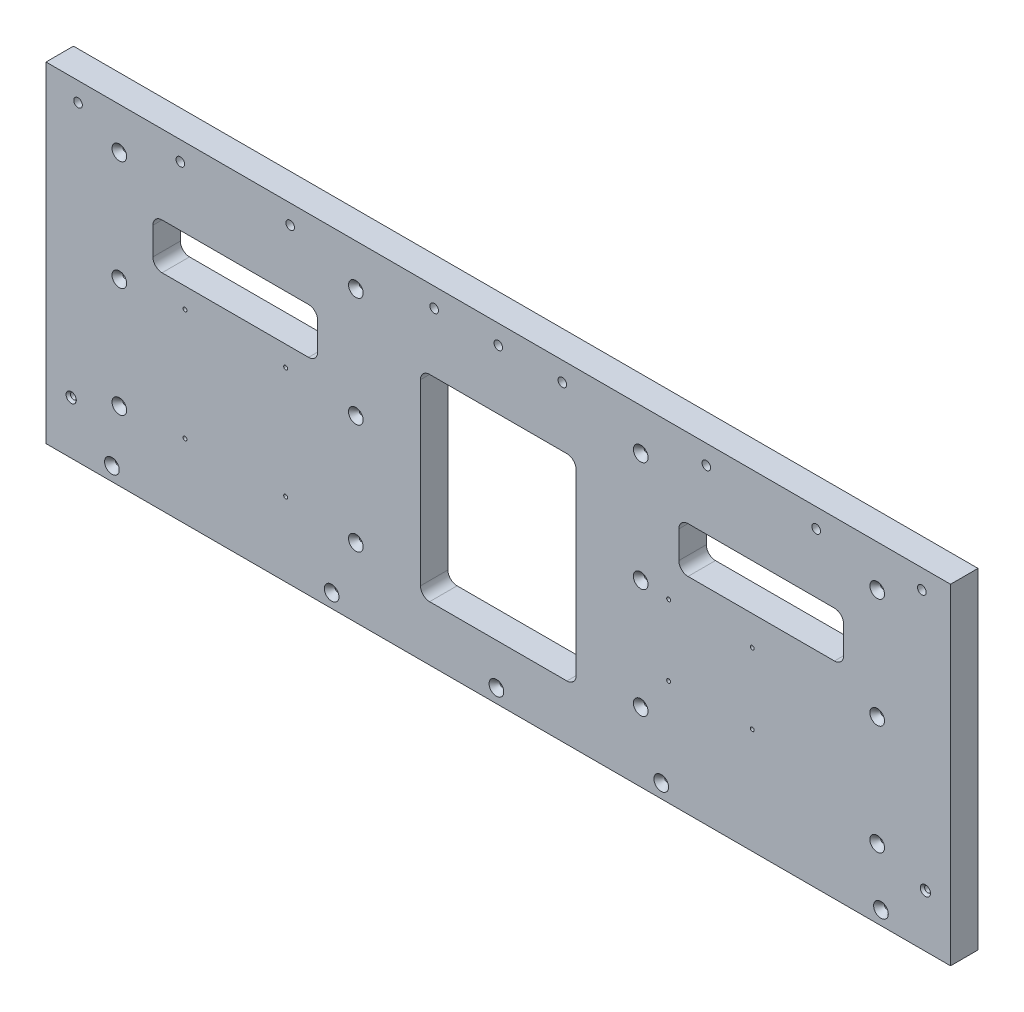
SolidWorks part; units mm, degrees
material "MDF"
ref_plane "Front Plane" through (0, 0, 0) normal (0, 0, 1) x (1, 0, 0)
ref_plane "Top Plane" through (0, 0, 0) normal (0, 1, 0) x (1, 0, 0)
ref_plane "Right Plane" through (0, 0, 0) normal (1, 0, 0) x (0, 0, -1)
sketch "Sketch1" plane through (0, 0, 0) normal (0, 0, 1) x (1, 0, 0)
  line L1 (-496.0937, -132.715) -> (131.2863, -132.715)
  line L2 (-496.0937, -132.715) -> (-496.0937, -361.95)
  line L3 (-496.0937, -361.95) -> (131.2863, -361.95)
  line L4 (131.2863, -132.715) -> (131.2863, -361.95)
  line L5 (-496.0937, -132.715) -> (-496.0937, -697.8385) construction
  line L7 (131.2863, -361.95) -> (131.2863, -342.9) construction
  line L12 (128.7463, -132.715) -> (-84.6137, -132.715) construction
  line L13 (-290.722, -342.9) -> (-271.672, -342.9) construction
  dimension "D1" = 19.05
extrude "Boss-Extrude1" add sketch "Sketch1" along normal blind 19.05
hole_wizard "5/64 (0.07813) Diameter Hole1" positions "Sketch5" profile "Sketch6" hole size "5/64" standard "ANSI Inch"
sketch "Sketch5" plane through (-182.4037, -6471.4599, 19.05) normal (0, 0, 1) x (1, 0, 0)
  line L1 (0, 6109.5099) -> (0, 6338.7449) construction
  point P0 (-262.8265, 6157.4524)
  point P6 (-98.7933, 6157.4524)
  point P18 (-262.8265, 6233.6524)
  point P19 (-98.7933, 6233.6524)
  point P22 (-262.8265, 6309.8524)
  point P23 (-98.7933, 6309.8524)
  point P24 (-267.97, 6119.0349)
  point P34 (-115.57, 6119.0349)
  point P37 (-1.27, 6119.0349)
  point P40 (113.03, 6119.0349)
  point P44 (265.43, 6119.0349)
  point P55 (98.7933, 6309.8524)
  point P56 (262.8265, 6309.8524)
  point P59 (98.7933, 6233.6524)
  point P60 (262.8265, 6233.6524)
  point P63 (98.7933, 6157.4524)
  point P64 (262.8265, 6157.4524)
sketch "Sketch6" plane through (-445.2302, -314.0075, 19.05) normal (1, 0, 0) x (0, -1, 0)
  line L0 (0, 0) -> (0, 39.0539)
  line L1 (0, 39.0539) -> (1.5875, 38.1)
  line L2 (1.5875, 38.1) -> (1.5875, 4.0177)
  line L3 (1.5875, 4.0177) -> (5.08, 0)
  line L4 (5.08, 0) -> (0, 0)
  line L5 (-1.5875, 4.0177) -> (-5.08, 0) construction
  line L6 (0, 39.0539) -> (-1.5875, 38.1) construction
  line L7 (0, -6.35) -> (0, 107.95) construction
  dimension "Hole Dia." = 3.175
  dimension "Hole Depth" = 38.1
  dimension "Near C'Sink Dia." = 10.16
  dimension "Near C'Sink Angle" = 82
  dimension "Drill Angle" = 118
hole_wizard "Diamètre du perçage 15/64 (0.23438)1" positions "Sketch7" profile "Sketch8" hole size "15/64" standard "Ansi Inch" end condition up to next
sketch "Sketch7" plane through (0, 0, 0) normal (0, 0, -1) x (-1, 0, 0)
  circle A0 centre (-111.4171, -146.05) radius 2.4574 construction
  point P0 (402.9075, -146.05)
  point P2 (326.7075, -146.05)
  point P4 (226.8537, -146.05)
  point P6 (182.4037, -146.05)
  point P8 (137.9537, -146.05)
  point P10 (38.1, -146.05)
  point P12 (-38.1, -146.05)
  point P13 (473.8687, -146.05)
  point P17 (-111.4171, -146.05)
  point P18 (0, 0)
  point P19 (0, 0)
  point P20 (0, 0)
  point P21 (0, 0)
  point P22 (-110.1721, -146.05)
sketch "Sketch8" plane through (-402.9075, -146.05, 0) normal (1, 0, 0) x (0, 1, 0)
  line L0 (0, 0) -> (0, 19.05)
  line L1 (0, 19.05) -> (2.9766, 19.05)
  line L2 (2.9766, 19.05) -> (2.9766, 0)
  line L5 (2.9766, 0) -> (0, 0)
  line L11 (0, -6.35) -> (0, 107.95) construction
  dimension "Thru Hole Dia." = 5.9533
  dimension "Thru Hole Depth" = 19.05
sketch "Sketch9" plane through (0, 0, 0) normal (0, 0, -1) x (-1, 0, 0)
  line L0 (0, -157.1498) -> (0, -342.9) construction
  line L1 (0, -250.0249) -> (93.1355, -250.0249) construction
  line L2 (61.3728, -330.2) -> (-61.3728, -330.2)
  line L3 (61.3728, -330.2) -> (61.3728, -169.8498)
  line L4 (61.3728, -169.8498) -> (-61.3728, -169.8498)
  line L5 (-61.3728, -330.2) -> (-61.3728, -169.8498)
  line L6 (61.3728, -330.2) -> (-61.3728, -169.8498) construction
  line L7 (61.3728, -169.8498) -> (-61.3728, -330.2) construction
  line L8 (93.1355, -250.0249) -> (271.672, -250.0249) construction
  line L9 (364.8075, -157.1625) -> (364.8075, -342.9) construction
  line L10 (258.972, -330.2) -> (105.8355, -330.2)
  line L11 (258.972, -330.2) -> (258.972, -169.8498)
  line L12 (258.972, -169.8498) -> (105.8355, -169.8498)
  line L13 (105.8355, -330.2) -> (105.8355, -169.8498)
  line L14 (258.972, -330.2) -> (105.8355, -169.8498) construction
  line L15 (258.972, -169.8498) -> (105.8355, -330.2) construction
  line L17 (426.1802, -330.2127) -> (303.4347, -330.2127)
  line L18 (426.1802, -330.2127) -> (426.1802, -169.8498)
  line L19 (426.1802, -169.8498) -> (303.4347, -169.8498)
  line L20 (303.4347, -330.2127) -> (303.4347, -169.8498)
  line L21 (426.1802, -330.2127) -> (303.4347, -169.8498) construction
  line L22 (426.1802, -169.8498) -> (303.4347, -330.2127) construction
  point P3 (0, -250.0249)
  point P8 (-74.0728, -342.9)
  point P13 (182.4037, -250.0249)
  point P20 (364.8075, -250.0313)
  dimension "D1" = 12.7
  dimension "D2" = 12.7
  dimension "D3" = 12.7
extrude "Cut-Extrude1" [suppressed] cut sketch "Sketch9" against normal up to next
fillet "Fillet1" [suppressed] radius 12.7
hole_wizard "#2 Clearance Hole1" positions "Sketch10" profile "Sketch11" hole size "#2" standard "ANSI Inch" end condition up to next
sketch "Sketch10" plane through (0, 0, 19.05) normal (0, 0, 1) x (1, 0, 0)
  point P2 (-6.2354, -239.6)
  point P4 (-64.2354, -239.6)
  point P6 (-64.2354, -288.6)
  point P8 (-6.2354, -288.6)
sketch "Sketch11" plane through (-6.2354, -239.6, 19.05) normal (1, 0, 0) x (0, -1, 0)
  line L0 (0, 0) -> (0, 19.05)
  line L1 (0, 19.05) -> (1.3525, 19.05)
  line L2 (1.3525, 19.05) -> (1.3525, 0)
  line L5 (1.3525, 0) -> (0, 0)
  line L11 (0, -6.35) -> (0, 107.95) construction
  dimension "Thru Hole Dia." = 2.7051
  dimension "Thru Hole Depth" = 19.05
hole_wizard "#2 Clearance Hole2" positions "Sketch12" profile "Sketch13" hole size "#2" standard "ANSI Inch" end condition up to next
sketch "Sketch12" plane through (0, 0, 0) normal (0, 0, -1) x (-1, 0, 0)
  point P0 (399.7261, -233.172)
  point P2 (329.8761, -233.172)
  point P4 (329.8761, -310.642)
  point P6 (399.7261, -310.642)
sketch "Sketch13" plane through (-399.7261, -233.172, 0) normal (1, 0, 0) x (0, 1, 0)
  line L0 (0, 0) -> (0, 19.05)
  line L1 (0, 19.05) -> (1.3525, 19.05)
  line L2 (1.3525, 19.05) -> (1.3525, 0)
  line L5 (1.3525, 0) -> (0, 0)
  line L11 (0, -6.35) -> (0, 107.95) construction
  dimension "Thru Hole Dia." = 2.7051
  dimension "Thru Hole Depth" = 19.05
hole_wizard "CSK for #6 Flat Head Machine Screw (100)1" positions "Sketch16" profile "Sketch17" countersink size "#6" standard "ANSI Inch" end condition up to next
sketch "Sketch16" plane through (0, 0, 19.05) normal (0, 0, 1) x (1, 0, 0)
  point P6 (113.8236, -325.4344)
  point P8 (-478.6312, -325.4375)
sketch "Sketch17" plane through (113.8236, -325.4344, 19.05) normal (1, 0, 0) x (0, -1, 0)
  line L0 (0, 0) -> (0, 19.05)
  line L1 (0, 19.05) -> (2.1526, 19.05)
  line L2 (2.1526, 19.05) -> (2.1526, 1.5998)
  line L3 (2.1526, 1.5998) -> (3.5433, 0)
  line L5 (3.5433, 0) -> (0, 0)
  line L6 (-2.1526, 1.5998) -> (-3.5433, 0) construction
  line L11 (0, -6.35) -> (0, 107.95) construction
  dimension "Thru Hole Dia." = 4.3053
  dimension "Thru Hole Depth" = 19.05
  dimension "Near C'Sink Dia." = 7.0866
  dimension "Near C'Sink Angle" = 82
sketch "Sketch18" plane through (0, 0, 0) normal (0, 0, -1) x (-1, 0, 0)
  line L0 (-74.0728, -171.45) -> (74.0855, -171.45) construction
  line L1 (-57.1437, -187.325) -> (57.1563, -187.325)
  line L2 (-57.1437, -187.325) -> (-57.1437, -219.075)
  line L3 (-57.1437, -219.075) -> (57.1563, -219.075)
  line L4 (57.1563, -187.325) -> (57.1563, -219.075)
  line L5 (-57.1437, -187.325) -> (57.1563, -219.075) construction
  line L6 (-57.1437, -219.075) -> (57.1563, -187.325) construction
  line L7 (496.0937, -361.95) -> (-131.2863, -361.95) construction
  line L8 (182.4037, -361.95) -> (182.4037, -132.715) construction
  line L9 (-131.2863, -132.715) -> (496.0937, -132.715) construction
  line L10 (421.9511, -187.325) -> (421.9511, -219.075)
  line L11 (421.9511, -219.075) -> (307.6511, -219.075)
  line L12 (307.6511, -187.325) -> (307.6511, -219.075)
  line L13 (421.9511, -187.325) -> (307.6511, -187.325)
  line L15 (236.3787, -323.85) -> (128.4287, -323.85)
  line L16 (236.3787, -323.85) -> (236.3787, -187.325)
  line L17 (236.3787, -187.325) -> (128.4287, -187.325)
  line L18 (128.4287, -323.85) -> (128.4287, -187.325)
  line L19 (236.3787, -323.85) -> (128.4287, -187.325) construction
  line L20 (236.3787, -187.325) -> (128.4287, -323.85) construction
  point P4 (0.0063, -203.2)
  point P8 (0.0063, -171.45)
  point P19 (182.4037, -255.5875)
  dimension "D1" = 114.3
  dimension "D2" = 31.75
  dimension "D3" = 158.75
  dimension "D4" = 38.1
  dimension "D6" = 107.95
extrude "Cut-Extrude2" cut sketch "Sketch18" against normal up to next
fillet "Fillet2" radius 6.35 12 edges at (-307.6511, -187.325, 9.525) (-307.6511, -219.075, 9.525) (-421.9511, -219.075, 9.525) (-421.9511, -187.325, 9.525) (-236.3787, -187.325, 9.525) (-236.3787, -323.85, 9.525) (-128.4287, -323.85, 9.525) (-128.4287, -187.325, 9.525) (-57.1563, -187.325, 9.525) (-57.1563, -219.075, 9.525) (57.1437, -219.075, 9.525) (57.1437, -187.325, 9.525)
